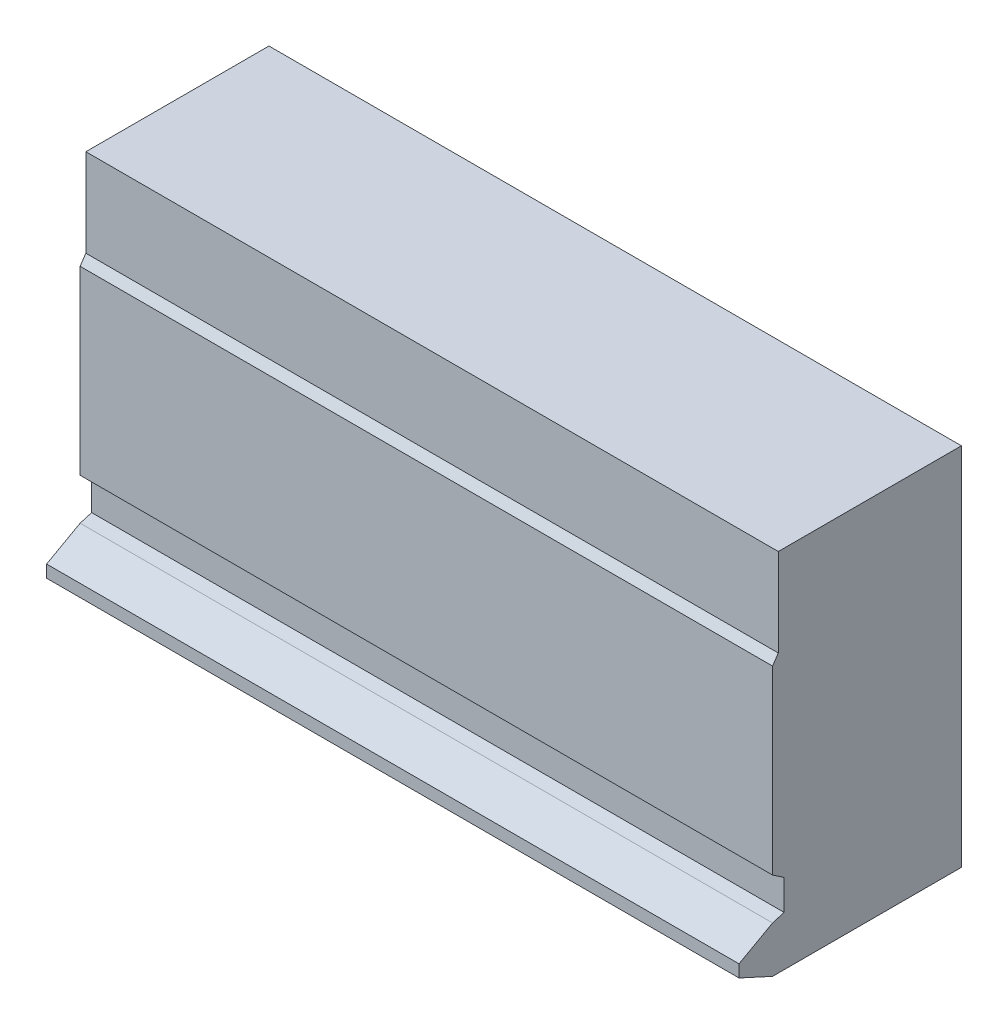
SolidWorks part; units mm, degrees
ref_plane "Front Plane" through (0, 0, 0) normal (0, 0, 1) x (1, 0, 0)
ref_plane "Top Plane" through (0, 0, 0) normal (0, 1, 0) x (1, 0, 0)
ref_plane "Right Plane" through (0, 0, 0) normal (1, 0, 0) x (0, 0, -1)
sketch "Sketch1" plane through (0, 0, 0) normal (0, 0, 1) x (1, 0, 0)
  line L1 (-47.9208, 29.5149) -> (62.0792, 29.5149)
  line L2 (-47.9208, 29.5149) -> (-47.9208, -28.4851)
  line L3 (-47.9208, -28.4851) -> (62.0792, -28.4851)
  line L4 (62.0792, 29.5149) -> (62.0792, -28.4851)
  dimension "D1" = 110
  dimension "D2" = 58
extrude "Boss-Extrude1" add sketch "Sketch1" along normal blind 30
sketch "Sketch2" plane through (-47.9208, 0, 0) normal (-1, 0, 0) x (0, 0, 1)
  line L0 (30, -21.1371) -> (35.3253, -24.0908)
  line L1 (30, 29.5149) -> (30, -28.4851) construction
  line L2 (35.3253, -24.0908) -> (35.3253, -26.0432)
  line L3 (35.3253, -26.0432) -> (30, -28.4851)
  line L4 (30, -28.4851) -> (30, -21.1371)
extrude "Boss-Extrude2" add sketch "Sketch2" against normal blind 110
sketch "Sketch3" plane through (-47.9208, 0, 0) normal (-1, 0, 0) x (0, 0, 1)
  line L0 (30, -21.1371) -> (28.1757, -20.5864)
  line L1 (28.1757, -20.5864) -> (28.1757, -15.7804)
  line L2 (28.1757, -15.7804) -> (30, -14.5431)
  line L3 (30, 29.5149) -> (30, -21.1371) construction
  line L4 (30, -14.5431) -> (30, 14.2069)
  line L5 (30, 14.2069) -> (29.0879, 15.5517)
  line L6 (29.0879, 15.5517) -> (29.0879, 31.8288)
  line L7 (29.0879, 31.8288) -> (32.7314, 31.8288)
  line L8 (32.7314, 31.8288) -> (32.7314, -21.1371)
  line L9 (32.7314, -21.1371) -> (30, -21.1371)
extrude "Cut-Extrude1" cut sketch "Sketch3" against normal blind 110
